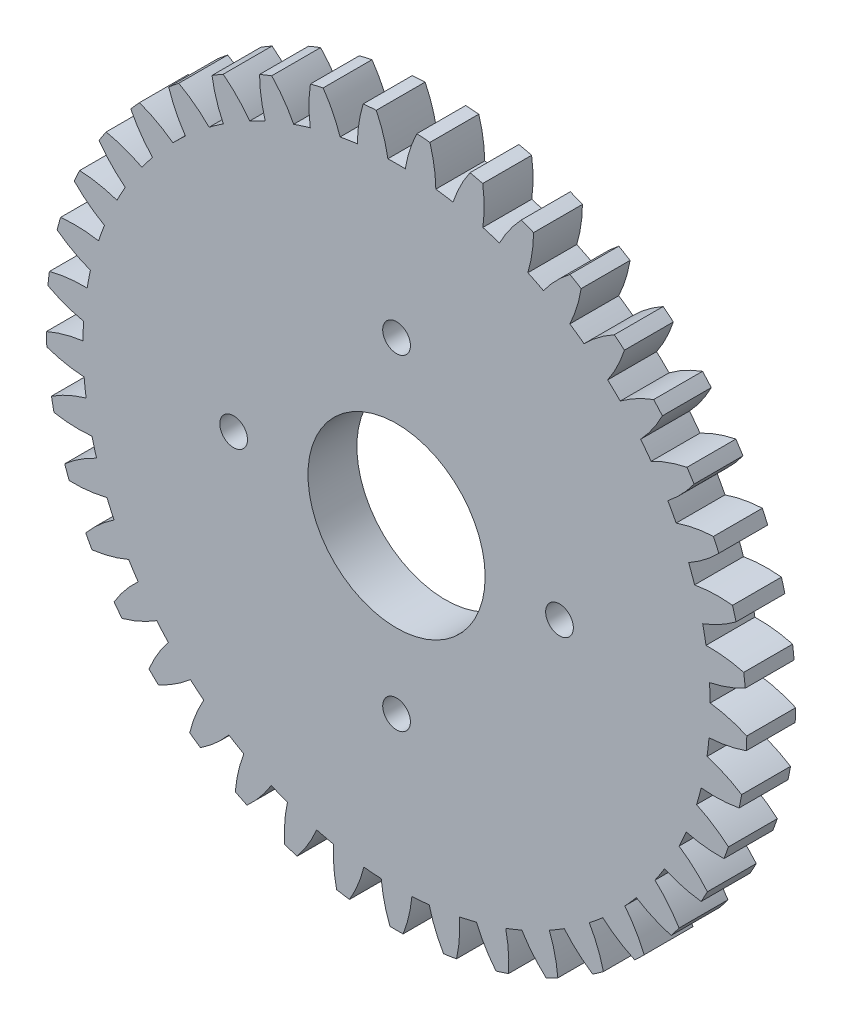
SolidWorks part; units mm, degrees
ref_plane "Alzado" through (0, 0, 0) normal (0, 0, 1) x (1, 0, 0)
ref_plane "Planta" through (0, 0, 0) normal (0, 1, 0) x (1, 0, 0)
ref_plane "Vista lateral" through (0, 0, 0) normal (1, 0, 0) x (0, 0, -1)
sketch "Model" plane through (0, 0, 0) normal (0, 0, 1) x (1, 0, 0)
  circle A0 centre (0, 0) radius 10.875
  circle A1 centre (-20, 0) radius 1.7
  circle A2 centre (0, -20) radius 1.7
  circle A3 centre (20, 0) radius 1.7
  circle A4 centre (0, 20) radius 1.7
  arc A5 (-37.9834, 6.2798) -> (-42.6167, 5.7289) centre (-38.3836, -10.1153) ccw
  arc A6 (-37.5772, 8.3743) -> (-37.9834, 6.2798) centre (0, 0) ccw
  arc A7 (-41.6686, 10.6172) -> (-37.5772, 8.3743) centre (-31.8196, 23.7304) ccw
  arc A8 (-41.2427, 12.1672) -> (-41.6686, 10.6172) centre (0, 0) ccw
  arc A9 (-36.5796, 12.0043) -> (-41.2427, 12.1672) centre (-39.4778, -4.1376) ccw
  arc A10 (-35.8584, 14.0123) -> (-36.5796, 12.0043) centre (0, 0) ccw
  arc A11 (-39.5596, 16.8535) -> (-35.8584, 14.0123) centre (-27.8242, 28.3095) ccw
  arc A12 (-38.902, 18.3203) -> (-39.5596, 16.8535) centre (0, 0) ccw
  arc A13 (-34.3185, 17.4475) -> (-38.902, 18.3203) centre (-39.6468, 1.9372) ccw
  arc A14 (-33.2992, 19.3219) -> (-34.3185, 17.4475) centre (0, 0) ccw
  arc A15 (-36.5233, 22.6947) -> (-33.2992, 19.3219) centre (-23.1767, 32.2251) ccw
  arc A16 (-35.6495, 24.0439) -> (-36.5233, 22.6947) centre (0, 0) ccw
  arc A17 (-31.2529, 22.4817) -> (-35.6495, 24.0439) centre (-38.8864, 7.9665) ccw
  arc A18 (-29.9595, 24.1785) -> (-31.2529, 22.4817) centre (0, 0) ccw
  arc A19 (-32.6309, 28.004) -> (-29.9595, 24.1785) centre (-17.9859, 35.3854) ccw
  arc A20 (-31.5614, 29.204) -> (-32.6309, 28.004) centre (0, 0) ccw
  arc A21 (-27.4548, 26.989) -> (-31.5614, 29.204) centre (-37.2146, 13.8092) ccw
  arc A22 (-25.9176, 28.4685) -> (-27.4548, 26.989) centre (0, 0) ccw
  arc A23 (-27.9737, 32.6569) -> (-25.9176, 28.4685) centre (-12.3736, 37.7162) ccw
  arc A24 (-26.7336, 33.6796) -> (-27.9737, 32.6569) centre (0, 0) ccw
  arc A25 (-23.0132, 30.8636) -> (-26.7336, 33.6796) centre (-34.6705, 19.3281) ccw
  arc A26 (-21.2681, 32.0911) -> (-23.0132, 30.8636) centre (0, 0) ccw
  arc A27 (-22.6608, 36.5443) -> (-21.2681, 32.0911) centre (-6.4712, 39.163) ccw
  arc A28 (-21.2791, 37.3658) -> (-22.6608, 36.5443) centre (0, 0) ccw
  arc A29 (-18.0322, 34.0149) -> (-21.2791, 37.3658) centre (-31.3137, 24.394) ccw
  arc A30 (-16.1202, 34.9616) -> (-18.0322, 34.0149) centre (0, 0) ccw
  arc A31 (-16.8168, 39.5752) -> (-16.1202, 34.9616) centre (-0.4172, 39.6919) ccw
  arc A32 (-15.3259, 40.1761) -> (-16.8168, 39.5752) centre (0, 0) ccw
  arc A33 (-12.6285, 36.3688) -> (-15.3259, 40.1761) centre (-27.223, 28.8881) ccw
  arc A34 (-10.5944, 37.0126) -> (-12.6285, 36.3688) centre (0, 0) ccw
  arc A35 (-10.5786, 41.6785) -> (-10.5944, 37.0126) centre (5.6466, 39.2904) ccw
  arc A36 (-9.0134, 42.0447) -> (-10.5786, 41.6785) centre (0, 0) ccw
  arc A37 (-6.9289, 37.8704) -> (-9.0134, 42.0447) centre (-22.4942, 32.7052) ccw
  arc A38 (-4.8203, 38.196) -> (-6.9289, 37.8704) centre (0, 0) ccw
  arc A39 (-4.0924, 42.8048) -> (-4.8203, 38.196) centre (11.5781, 37.968) ccw
  arc A40 (-2.4897, 42.9279) -> (-4.0924, 42.8048) centre (0, 0) ccw
  arc A41 (-1.0668, 38.4842) -> (-2.4897, 42.9279) centre (-17.2382, 35.7556) ccw
  arc A42 (1.0668, 38.4842) -> (-1.0668, 38.4842) centre (0, 0) ccw
  arc A43 (2.4897, 42.9279) -> (1.0668, 38.4842) centre (17.2382, 35.7556) ccw
  arc A44 (4.0924, 42.8048) -> (2.4897, 42.9279) centre (0, 0) ccw
  arc A45 (4.8203, 38.196) -> (4.0924, 42.8048) centre (-11.5781, 37.968) ccw
  arc A46 (6.9289, 37.8704) -> (4.8203, 38.196) centre (0, 0) ccw
  arc A47 (9.0134, 42.0447) -> (6.9289, 37.8704) centre (22.4942, 32.7052) ccw
  arc A48 (10.5786, 41.6785) -> (9.0134, 42.0447) centre (0, 0) ccw
  arc A49 (10.5944, 37.0126) -> (10.5786, 41.6785) centre (-5.6466, 39.2904) ccw
  arc A50 (12.6285, 36.3688) -> (10.5944, 37.0126) centre (0, 0) ccw
  arc A51 (15.3259, 40.1761) -> (12.6285, 36.3688) centre (27.223, 28.8881) ccw
  arc A52 (16.8168, 39.5752) -> (15.3259, 40.1761) centre (0, 0) ccw
  arc A53 (16.1202, 34.9616) -> (16.8168, 39.5752) centre (0.4172, 39.6919) ccw
  arc A54 (18.0322, 34.0149) -> (16.1202, 34.9616) centre (0, 0) ccw
  arc A55 (21.2791, 37.3658) -> (18.0322, 34.0149) centre (31.3137, 24.394) ccw
  arc A56 (22.6608, 36.5443) -> (21.2791, 37.3658) centre (0, 0) ccw
  arc A57 (21.2681, 32.0911) -> (22.6608, 36.5443) centre (6.4712, 39.163) ccw
  arc A58 (23.0132, 30.8636) -> (21.2681, 32.0911) centre (0, 0) ccw
  arc A59 (26.7336, 33.6796) -> (23.0132, 30.8636) centre (34.6705, 19.3281) ccw
  arc A60 (27.9737, 32.6569) -> (26.7336, 33.6796) centre (0, 0) ccw
  arc A61 (25.9176, 28.4685) -> (27.9737, 32.6569) centre (12.3736, 37.7162) ccw
  arc A62 (27.4548, 26.989) -> (25.9176, 28.4685) centre (0, 0) ccw
  arc A63 (31.5614, 29.204) -> (27.4548, 26.989) centre (37.2146, 13.8092) ccw
  arc A64 (32.6309, 28.004) -> (31.5614, 29.204) centre (0, 0) ccw
  arc A65 (29.9595, 24.1785) -> (32.6309, 28.004) centre (17.9859, 35.3854) ccw
  arc A66 (31.2529, 22.4817) -> (29.9595, 24.1785) centre (0, 0) ccw
  arc A67 (35.6495, 24.0439) -> (31.2529, 22.4817) centre (38.8864, 7.9665) ccw
  arc A68 (36.5233, 22.6947) -> (35.6495, 24.0439) centre (0, 0) ccw
  arc A69 (33.2992, 19.3219) -> (36.5233, 22.6947) centre (23.1767, 32.2251) ccw
  arc A70 (34.3185, 17.4475) -> (33.2992, 19.3219) centre (0, 0) ccw
  arc A71 (38.902, 18.3203) -> (34.3185, 17.4475) centre (39.6468, 1.9372) ccw
  arc A72 (39.5596, 16.8535) -> (38.902, 18.3203) centre (0, 0) ccw
  arc A73 (35.8584, 14.0123) -> (39.5596, 16.8535) centre (27.8242, 28.3095) ccw
  arc A74 (36.5796, 12.0043) -> (35.8584, 14.0123) centre (0, 0) ccw
  arc A75 (41.2427, 12.1672) -> (36.5796, 12.0043) centre (39.4778, -4.1376) ccw
  arc A76 (41.6686, 10.6172) -> (41.2427, 12.1672) centre (0, 0) ccw
  arc A77 (37.5772, 8.3743) -> (41.6686, 10.6172) centre (31.8196, 23.7304) ccw
  arc A78 (37.9834, 6.2798) -> (37.5772, 8.3743) centre (0, 0) ccw
  arc A79 (42.6167, 5.7289) -> (37.9834, 6.2798) centre (38.3836, -10.1153) ccw
  arc A80 (42.801, 4.1321) -> (42.6167, 5.7289) centre (0, 0) ccw
  arc A81 (38.4151, 2.54) -> (42.801, 4.1321) centre (35.0691, 18.5951) ccw
  arc A82 (38.4968, 0.4081) -> (38.4151, 2.54) centre (0, 0) ccw
  arc A83 (42.9917, -0.8436) -> (38.4968, 0.4081) centre (36.3896, -15.856) ccw
  arc A84 (42.9302, -2.4499) -> (42.9917, -0.8436) centre (0, 0) ccw
  arc A85 (38.3526, -3.3538) -> (42.9302, -2.4499) centre (37.4966, 13.0239) ccw
  arc A86 (38.108, -5.4732) -> (38.3526, -3.3538) centre (0, 0) ccw
  arc A87 (42.3591, -7.3964) -> (38.108, -5.4732) centre (33.5427, -21.225) ccw
  arc A88 (42.0531, -8.9744) -> (42.3591, -7.3964) centre (0, 0) ccw
  arc A89 (37.3912, -9.169) -> (42.0531, -8.9744) centre (39.0453, 7.1474) ccw
  arc A90 (36.8259, -11.2263) -> (37.3912, -9.169) centre (0, 0) ccw
  arc A91 (40.7336, -13.7758) -> (36.8259, -11.2263) centre (29.9097, -26.0966) ccw
  arc A92 (40.1903, -15.2886) -> (40.7336, -13.7758) centre (0, 0) ccw
  arc A93 (35.5534, -14.7692) -> (40.1903, -15.2886) centre (39.6787, 1.1034) ccw
  arc A94 (34.6806, -16.7161) -> (35.5534, -14.7692) centre (0, 0) ccw
  arc A95 (38.1534, -19.8323) -> (34.6806, -16.7161) centre (25.5755, -30.3564) ccw
  arc A96 (37.3855, -21.2444) -> (38.1534, -19.8323) centre (0, 0) ccw
  arc A97 (32.8822, -20.0234) -> (37.3855, -21.2444) centre (39.3821, -4.9664) ccw
  arc A98 (31.7225, -21.8142) -> (32.8822, -20.0234) centre (0, 0) ccw
  arc A99 (34.6789, -25.4239) -> (31.7225, -21.8142) centre (20.6419, -33.9047) ccw
  arc A100 (33.7044, -26.7023) -> (34.6789, -25.4239) centre (0, 0) ccw
  arc A101 (29.4403, -24.8081) -> (33.7044, -26.7023) centre (38.1625, -10.9199) ccw
  arc A102 (28.0208, -26.4009) -> (29.4403, -24.8081) centre (0, 0) ccw
  arc A103 (30.3915, -30.4197) -> (28.0208, -26.4009) centre (15.2244, -36.6583) ccw
  arc A104 (29.2333, -31.5343) -> (30.3915, -30.4197) centre (0, 0) ccw
  arc A105 (25.3083, -29.0114) -> (29.2333, -31.5343) centre (36.0483, -16.6174) ccw
  arc A106 (23.6623, -30.3689) -> (25.3083, -29.0114) centre (0, 0) ccw
  arc A107 (25.3918, -34.7024) -> (23.6623, -30.3689) centre (9.4501, -38.5527) ccw
  arc A108 (24.077, -35.6272) -> (25.3918, -34.7024) centre (0, 0) ccw
  arc A109 (20.5831, -32.5347) -> (24.077, -35.6272) centre (33.0892, -21.9254) ccw
  arc A110 (18.7492, -33.625) -> (20.5831, -32.5347) centre (0, 0) ccw
  arc A111 (19.7969, -38.1718) -> (18.7492, -33.625) centre (3.4543, -39.5435) ccw
  arc A112 (18.3564, -38.885) -> (19.7969, -38.1718) centre (0, 0) ccw
  arc A113 (15.3755, -35.2954) -> (18.3564, -38.885) centre (29.3545, -26.7195) ccw
  arc A114 (13.3966, -36.093) -> (15.3755, -35.2954) centre (0, 0) ccw
  arc A115 (13.738, -40.7464) -> (13.3966, -36.093) centre (-2.6224, -39.6073) ccw
  arc A116 (12.2055, -41.2314) -> (13.738, -40.7464) centre (0, 0) ccw
  arc A117 (9.8075, -37.2288) -> (12.2055, -41.2314) centre (24.9318, -30.8873) ccw
  arc A118 (7.73, -37.715) -> (9.8075, -37.2288) centre (0, 0) ccw
  arc A119 (7.3571, -42.3659) -> (7.73, -37.715) centre (-8.6377, -38.7428) ccw
  arc A120 (5.7685, -42.6113) -> (7.3571, -42.3659) centre (0, 0) ccw
  arc A121 (4.0096, -38.2896) -> (5.7685, -42.6113) centre (19.9247, -34.3311) ccw
  arc A122 (1.8823, -38.453) -> (4.0096, -38.2896) centre (0, 0) ccw
  arc A123 (0.8037, -42.9925) -> (1.8823, -38.453) centre (-14.4506, -36.9703) ccw
  arc A124 (-0.8037, -42.9925) -> (0.8037, -42.9925) centre (0, 0) ccw
  arc A125 (-1.8823, -38.453) -> (-0.8037, -42.9925) centre (14.4506, -36.9703) ccw
  arc A126 (-4.0096, -38.2896) -> (-1.8823, -38.453) centre (0, 0) ccw
  arc A127 (-5.7685, -42.6113) -> (-4.0096, -38.2896) centre (-19.9247, -34.3311) ccw
  arc A128 (-7.3571, -42.3659) -> (-5.7685, -42.6113) centre (0, 0) ccw
  arc A129 (-7.73, -37.715) -> (-7.3571, -42.3659) centre (8.6377, -38.7428) ccw
  arc A130 (-9.8075, -37.2288) -> (-7.73, -37.715) centre (0, 0) ccw
  arc A131 (-12.2055, -41.2314) -> (-9.8075, -37.2288) centre (-24.9318, -30.8873) ccw
  arc A132 (-13.738, -40.7464) -> (-12.2055, -41.2314) centre (0, 0) ccw
  arc A133 (-13.3966, -36.093) -> (-13.738, -40.7464) centre (2.6224, -39.6073) ccw
  arc A134 (-15.3755, -35.2954) -> (-13.3966, -36.093) centre (0, 0) ccw
  arc A135 (-18.3564, -38.885) -> (-15.3755, -35.2954) centre (-29.3545, -26.7195) ccw
  arc A136 (-19.7969, -38.1718) -> (-18.3564, -38.885) centre (0, 0) ccw
  arc A137 (-18.7492, -33.625) -> (-19.7969, -38.1718) centre (-3.4543, -39.5435) ccw
  arc A138 (-20.5831, -32.5347) -> (-18.7492, -33.625) centre (0, 0) ccw
  arc A139 (-24.077, -35.6272) -> (-20.5831, -32.5347) centre (-33.0892, -21.9254) ccw
  arc A140 (-25.3918, -34.7024) -> (-24.077, -35.6272) centre (0, 0) ccw
  arc A141 (-23.6623, -30.3689) -> (-25.3918, -34.7024) centre (-9.4501, -38.5527) ccw
  arc A142 (-25.3083, -29.0114) -> (-23.6623, -30.3689) centre (0, 0) ccw
  arc A143 (-29.2333, -31.5343) -> (-25.3083, -29.0114) centre (-36.0483, -16.6174) ccw
  arc A144 (-30.3915, -30.4197) -> (-29.2333, -31.5343) centre (0, 0) ccw
  arc A145 (-28.0208, -26.4009) -> (-30.3915, -30.4197) centre (-15.2244, -36.6583) ccw
  arc A146 (-29.4403, -24.8081) -> (-28.0208, -26.4009) centre (0, 0) ccw
  arc A147 (-33.7044, -26.7023) -> (-29.4403, -24.8081) centre (-38.1625, -10.9199) ccw
  arc A148 (-34.6789, -25.4239) -> (-33.7044, -26.7023) centre (0, 0) ccw
  arc A149 (-31.7225, -21.8142) -> (-34.6789, -25.4239) centre (-20.6419, -33.9047) ccw
  arc A150 (-32.8822, -20.0234) -> (-31.7225, -21.8142) centre (0, 0) ccw
  arc A151 (-37.3855, -21.2444) -> (-32.8822, -20.0234) centre (-39.3821, -4.9664) ccw
  arc A152 (-38.1534, -19.8323) -> (-37.3855, -21.2444) centre (0, 0) ccw
  arc A153 (-34.6806, -16.7161) -> (-38.1534, -19.8323) centre (-25.5755, -30.3564) ccw
  arc A154 (-35.5534, -14.7692) -> (-34.6806, -16.7161) centre (0, 0) ccw
  arc A155 (-40.1903, -15.2886) -> (-35.5534, -14.7692) centre (-39.6787, 1.1034) ccw
  arc A156 (-40.7336, -13.7758) -> (-40.1903, -15.2886) centre (0, 0) ccw
  arc A157 (-36.8259, -11.2263) -> (-40.7336, -13.7758) centre (-29.9097, -26.0966) ccw
  arc A158 (-37.3912, -9.169) -> (-36.8259, -11.2263) centre (0, 0) ccw
  arc A159 (-42.0531, -8.9744) -> (-37.3912, -9.169) centre (-39.0453, 7.1474) ccw
  arc A160 (-42.3591, -7.3964) -> (-42.0531, -8.9744) centre (0, 0) ccw
  arc A161 (-38.108, -5.4732) -> (-42.3591, -7.3964) centre (-33.5427, -21.225) ccw
  arc A162 (-38.3526, -3.3538) -> (-38.108, -5.4732) centre (0, 0) ccw
  arc A163 (-42.9302, -2.4499) -> (-38.3526, -3.3538) centre (-37.4966, 13.0239) ccw
  arc A164 (-42.9917, -0.8436) -> (-42.9302, -2.4499) centre (0, 0) ccw
  arc A165 (-38.4968, 0.4081) -> (-42.9917, -0.8436) centre (-36.3896, -15.856) ccw
  arc A166 (-38.4151, 2.54) -> (-38.4968, 0.4081) centre (0, 0) ccw
  arc A167 (-42.801, 4.1321) -> (-38.4151, 2.54) centre (-35.0691, 18.5951) ccw
  arc A168 (-42.6167, 5.7289) -> (-42.801, 4.1321) centre (0, 0) ccw
  text T0 "Producto SOLIDWORKS Educational." font "SWTXT" height 4.8336
  text T1 "Solo para uso en la enseñanza." font "SWTXT" height 4.8336
extrude "Saliente-Extruir1" add sketch "Model" along normal blind 6
sketch "Croquis2" plane through (0, 0, 6) normal (0, 0, 1) x (1, 0, 0)
  line L1 (-45.4445, -43.6129) -> (64.2012, -43.6129)
  line L2 (-45.4445, -43.6129) -> (-45.4445, -60.7381)
  line L3 (-45.4445, -60.7381) -> (64.2012, -60.7381)
  line L4 (64.2012, -43.6129) -> (64.2012, -60.7381)
extrude "Cortar-Extruir1" cut sketch "Croquis2" against normal blind 10
